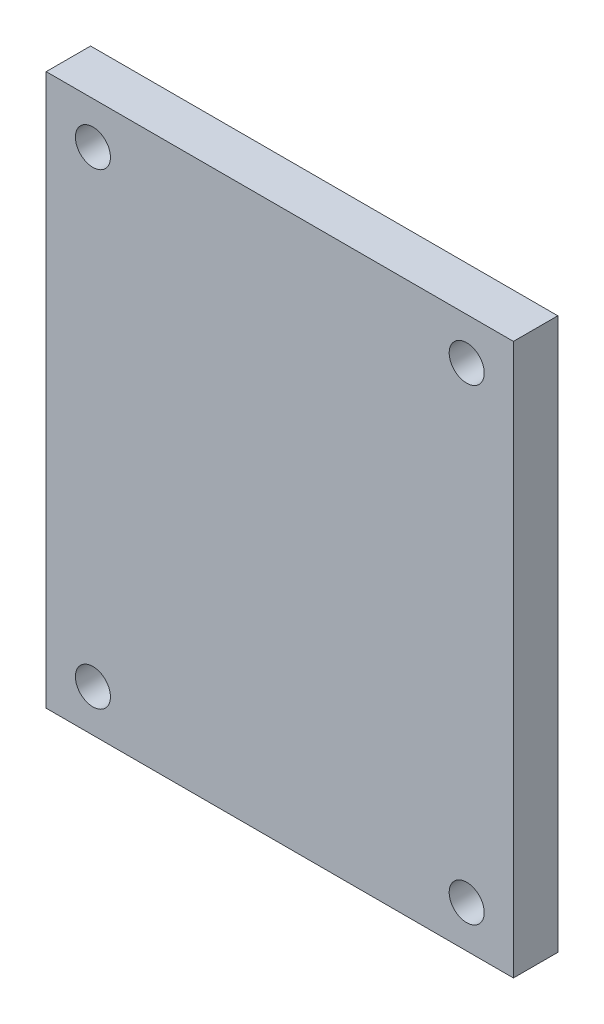
SolidWorks part; units mm, degrees
ref_plane "Front Plane" through (0, 0, 0) normal (0, 0, 1) x (1, 0, 0)
ref_plane "Top Plane" through (0, 0, 0) normal (0, 1, 0) x (1, 0, 0)
ref_plane "Right Plane" through (0, 0, 0) normal (1, 0, 0) x (0, 0, -1)
sketch "Sketch1" plane through (0, 0, 0) normal (0, 0, 1) x (1, 0, 0)
  line L0 (5.08, 55.372) -> (5.08, 4.572) construction
  line L1 (0, 0) -> (50.8, 0)
  line L2 (0, 0) -> (0, 59.944)
  line L3 (0, 59.944) -> (50.8, 59.944)
  line L4 (50.8, 0) -> (50.8, 59.944)
  line L5 (0, 29.972) -> (50.8, 29.972) construction
  line L6 (25.4, 59.944) -> (25.4, 29.972) construction
  circle A0 centre (5.08, 55.372) radius 1.905
  circle A1 centre (5.08, 4.572) radius 1.905
  circle A2 centre (45.72, 55.372) radius 1.905
  circle A3 centre (45.72, 4.572) radius 1.905
  dimension "D3" = 3.81
  dimension "D4" = 3.81
  dimension "D6" = 3.81
  dimension "D8" = 3.81
  dimension "D1" = 59.944
  dimension "D2" = 50.8
  dimension "D5" = 50.8
  dimension "D7" = 40.64
  dimension "D9" = 40.64
  dimension "D10" = 50.8
  dimension "D11" = 25.4
  dimension "D12" = 20.32
extrude "Boss-Extrude1" add sketch "Sketch1" along normal blind 4.826
equation "\"MDF\"= 0.19in"
equation "\"PVCID\" = 2.067in"
equation "\"PVCOD\" = 2.375in"
equation "\"GenDiameter\"= 60mm"
equation "\"GenCutDiameter\" = 1.8in"
equation "\"GenCutDistance\" = 1"
equation "\"TowerHeight\" = 6in"
equation "\"TowerFrontBase\" = 3in"
equation "\"FunnelHeight\" = 1in"
equation "\"FunnelAngle\" = 20"
equation "\"TowerSideBase\" = 3in"
equation "\"TowerPanelLength\" = 2in"
equation "\"TowerPanelLeeway\" = 0.5in"
equation "\"BaseLength\" = 9in"
equation "\"BaseWidth\" = 10in"
equation "\"WheelHoleLength\" = 3.25in"
equation "\"WheelHoleWidth\" = 26mm"
equation "\"WheelHoleFromBack\" = 1in"
equation "\"DropLength\" = 1in"
equation "\"DropWidth\" = 8.5in"
equation "\"BumperWidth\" = 1in"
equation "\"SmallHexDiameter\" = 0.185in"
equation "\"SmallHexHeight\" = 0.701in"
equation "\"ScrewSize\" = 0.106in"
equation "\"BigHexDiameter\" = 0.251in"
equation "\"BigHexHeight\" = 0.374in"
equation "\"PCBThickness\" = 0.066in"
equation "\"ConnectorHeight\" = 0.517in"
equation "\"BoardHeight\" = 0.583in"
equation "\"UnoStackHeight\" = 1.351in"
equation "\"UnoStackWidth\" = 3.053in"
equation "\"UnoStackLength\" = 3.152in"
equation "\"HBridgeWidth\" = 1.797in"
equation "\"HBridgeLength\" = 2.236in"
equation "\"DSWidth\" = 1.820in"
equation "\"DSLength\" = 1.833in"
equation "\"StepperWidth\" = 1.799in"
equation "\"StepperLength\" = 2.248in"
equation "\"ULNWidth\" = 1.304in"
equation "\"ULNLength\" = 1.545in"
equation "\"VSwitchHeight\" = 0.392in"
equation "\"VSwitchWidth\" = 0.637in"
equation "\"VSwitchLength\" = 1.097in"
equation "\"SkateWheelDiameter\" = 80mm"
equation "\"SkateWheelThickness\" = 24mm"
equation "\"BaseDistance\" = 3in"
equation "\"DummyVar\" = 2in"
equation "\"D1@Boss-Extrude1\"=\"MDF\""
